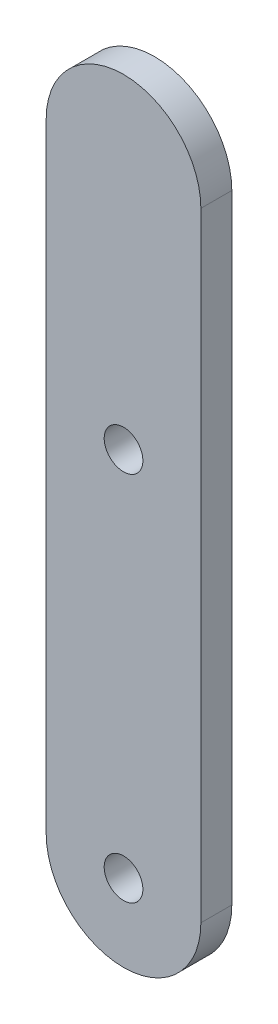
SolidWorks part; units mm, degrees
material "Alloy Steel"
ref_plane "Front Plane" through (0, 0, 0) normal (0, 0, 1) x (1, 0, 0)
ref_plane "Top Plane" through (0, 0, 0) normal (0, 1, 0) x (1, 0, 0)
ref_plane "Right Plane" through (0, 0, 0) normal (1, 0, 0) x (0, 0, -1)
other "Configuration Table"
sketch "Sketch1" plane through (0, 0, 0) normal (0, 0, 1) x (1, 0, 0)
  line L0 (0, 0) -> (0, 40) construction
  line L1 (-5, 0) -> (-5, 40)
  line L2 (5, 0) -> (5, 40)
  arc A0 (-5, 0) -> (5, 0) centre (0, 0) ccw
  arc A1 (5, 40) -> (-5, 40) centre (0, 40) ccw
  circle A2 centre (0, 0) radius 1.25
  circle A3 centre (0, 24) radius 1.25
  point P3 (0, 20)
  dimension "D1" = 2.5
  dimension "D2" = 40
  dimension "D3" = 10
  dimension "D4" = 24
extrude "Boss-Extrude1" add sketch "Sketch1" along normal blind 2
ref_axis "Axis1" through (0, 24, 2) along (0, 0, -1)
ref_plane "Plane1" through (0, 24, 0) normal (0, 1, 0) x (-1, 0, 0)
